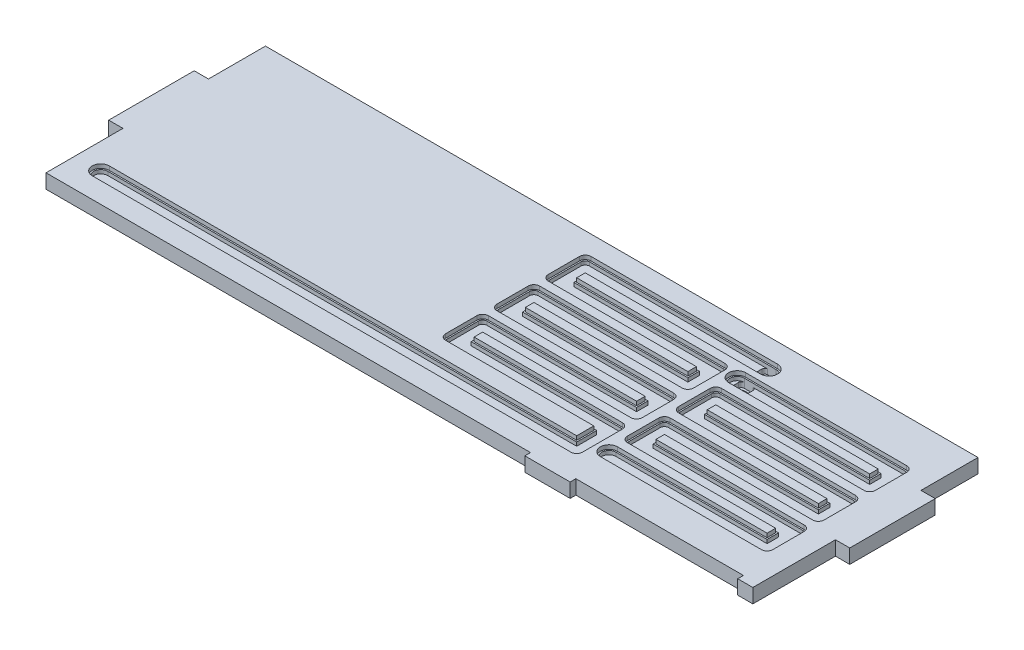
SolidWorks part; units mm, degrees
ref_plane "前视基准面" through (0, 0, 0) normal (0, 0, 1) x (1, 0, 0)
ref_plane "上视基准面" through (0, 0, 0) normal (0, 1, 0) x (1, 0, 0)
ref_plane "右视基准面" through (0, 0, 0) normal (1, 0, 0) x (0, 0, -1)
sketch "草图1" plane through (0, 0, 0) normal (0, 1, 0) x (1, 0, 0)
  line L0 (0, 0) -> (0, -200)
  line L1 (0, -200) -> (-50, -200)
  line L2 (-50, -200) -> (-50, -500)
  line L3 (-50, -500) -> (0, -500)
  line L4 (0, -500) -> (0, -770)
  line L5 (0, -770) -> (1700, -770)
  line L6 (1700, -770) -> (1700, -790)
  line L7 (1700, -790) -> (1859, -790)
  line L8 (1859, -790) -> (1859, -770)
  line L9 (1859, -770) -> (2447, -770)
  line L10 (2447, -770) -> (2447, -790)
  line L11 (2447, -790) -> (2500, -790)
  line L12 (2500, -790) -> (2500, -500)
  line L13 (2500, -500) -> (2550, -500)
  line L14 (2550, -500) -> (2550, -200)
  line L15 (2550, -200) -> (2500, -200)
  line L16 (2500, -200) -> (2500, 0)
  line L17 (2500, 0) -> (0, 0)
  line L18 (90, -668) -> (1760, -668)
  line L19 (1760, -668) -> (1760, -548)
  line L20 (1760, -548) -> (1220, -548)
  line L21 (1220, -548) -> (1220, -458)
  line L22 (1220, -458) -> (1760, -458)
  line L23 (1760, -458) -> (1760, -368)
  line L24 (1760, -368) -> (1220, -368)
  line L25 (1220, -368) -> (1220, -278)
  line L26 (1220, -278) -> (1760, -278)
  line L27 (1760, -278) -> (1760, -188)
  line L28 (1760, -188) -> (1220, -188)
  line L29 (1220, -188) -> (1220, -98)
  line L30 (1220, -98) -> (1865, -98)
  line L31 (1835, -180) -> (2390, -180)
  line L32 (2390, -180) -> (2390, -270)
  line L33 (2390, -270) -> (1850, -270)
  line L34 (1850, -270) -> (1850, -360)
  line L35 (1850, -360) -> (2390, -360)
  line L36 (2390, -360) -> (2390, -450)
  line L37 (2390, -450) -> (1850, -450)
  line L38 (1850, -450) -> (1850, -540)
  line L39 (1850, -540) -> (2390, -540)
  line L40 (2390, -540) -> (2390, -630)
  line L41 (2390, -630) -> (1835, -630)
  line L42 (90, -698) -> (1770, -698)
  line L43 (1790, -678) -> (1790, -538)
  line L44 (1770, -518) -> (1250, -518)
  line L45 (1250, -518) -> (1250, -488)
  line L46 (1250, -488) -> (1770, -488)
  line L47 (1790, -468) -> (1790, -358)
  line L48 (1770, -338) -> (1250, -338)
  line L49 (1250, -338) -> (1250, -308)
  line L50 (1250, -308) -> (1770, -308)
  line L51 (1790, -288) -> (1790, -178)
  line L52 (1770, -158) -> (1250, -158)
  line L53 (1250, -158) -> (1250, -128)
  line L54 (1250, -128) -> (1865, -128)
  line L55 (90, -638) -> (1730, -638)
  line L56 (1730, -638) -> (1730, -578)
  line L57 (1730, -578) -> (1210, -578)
  line L58 (1190, -558) -> (1190, -448)
  line L59 (1210, -428) -> (1730, -428)
  line L60 (1730, -428) -> (1730, -398)
  line L61 (1730, -398) -> (1210, -398)
  line L62 (1190, -378) -> (1190, -268)
  line L63 (1210, -248) -> (1730, -248)
  line L64 (1730, -248) -> (1730, -218)
  line L65 (1730, -218) -> (1210, -218)
  line L66 (1190, -198) -> (1190, -88)
  line L67 (1210, -68) -> (1865, -68)
  line L68 (1790, -308) -> (1790, -158) construction
  line L69 (1790, -158) -> (1250, -158) construction
  line L70 (1250, -308) -> (1790, -308) construction
  line L71 (1790, -488) -> (1790, -338) construction
  line L72 (1790, -338) -> (1250, -338) construction
  line L73 (1250, -488) -> (1790, -488) construction
  line L74 (1790, -698) -> (1790, -518) construction
  line L75 (1790, -518) -> (1250, -518) construction
  line L76 (90, -698) -> (1790, -698) construction
  line L77 (1730, -578) -> (1190, -578) construction
  line L78 (1190, -578) -> (1190, -428) construction
  line L79 (1190, -428) -> (1730, -428) construction
  line L80 (1730, -398) -> (1190, -398) construction
  line L81 (1190, -398) -> (1190, -248) construction
  line L82 (1190, -248) -> (1730, -248) construction
  line L83 (1730, -218) -> (1190, -218) construction
  line L84 (1190, -218) -> (1190, -68) construction
  line L85 (1190, -68) -> (1865, -68) construction
  line L86 (90, -693) -> (1770, -693)
  line L87 (1785, -678) -> (1785, -538)
  line L88 (1770, -523) -> (1245, -523)
  line L89 (1245, -523) -> (1245, -483)
  line L90 (1245, -483) -> (1770, -483)
  line L91 (1785, -468) -> (1785, -358)
  line L92 (1770, -343) -> (1245, -343)
  line L93 (1245, -343) -> (1245, -303)
  line L94 (1245, -303) -> (1770, -303)
  line L95 (1785, -288) -> (1785, -178)
  line L96 (1770, -163) -> (1245, -163)
  line L97 (1245, -163) -> (1245, -123)
  line L98 (1245, -123) -> (1865, -123)
  line L99 (1210, -73) -> (1865, -73)
  line L100 (1195, -198) -> (1195, -88)
  line L101 (1735, -213) -> (1210, -213)
  line L102 (1735, -253) -> (1735, -213)
  line L103 (1210, -253) -> (1735, -253)
  line L104 (1195, -378) -> (1195, -268)
  line L105 (1735, -393) -> (1210, -393)
  line L106 (1735, -433) -> (1735, -393)
  line L107 (1210, -433) -> (1735, -433)
  line L108 (1195, -558) -> (1195, -448)
  line L109 (1735, -573) -> (1210, -573)
  line L110 (1735, -643) -> (1735, -573)
  line L111 (90, -643) -> (1735, -643)
  line L112 (1835, -210) -> (2360, -210)
  line L113 (2360, -210) -> (2360, -240)
  line L114 (2360, -240) -> (1840, -240)
  line L115 (1820, -260) -> (1820, -370)
  line L116 (1840, -390) -> (2360, -390)
  line L117 (2360, -390) -> (2360, -420)
  line L118 (2360, -420) -> (1840, -420)
  line L119 (1820, -440) -> (1820, -550)
  line L120 (1840, -570) -> (2360, -570)
  line L121 (2360, -570) -> (2360, -600)
  line L122 (2360, -600) -> (1835, -600)
  line L123 (1835, -150) -> (2400, -150)
  line L124 (2420, -170) -> (2420, -280)
  line L125 (2400, -300) -> (1880, -300)
  line L126 (1880, -300) -> (1880, -330)
  line L127 (1880, -330) -> (2400, -330)
  line L128 (2420, -350) -> (2420, -460)
  line L129 (2400, -480) -> (1880, -480)
  line L130 (1880, -480) -> (1880, -510)
  line L131 (1880, -510) -> (2400, -510)
  line L132 (2420, -530) -> (2420, -640)
  line L133 (2400, -660) -> (1835, -660)
  line L134 (2360, -240) -> (1820, -240) construction
  line L135 (1820, -240) -> (1820, -390) construction
  line L136 (1820, -390) -> (2360, -390) construction
  line L137 (2360, -420) -> (1820, -420) construction
  line L138 (1820, -420) -> (1820, -570) construction
  line L139 (1820, -570) -> (2360, -570) construction
  line L140 (2420, -510) -> (2420, -660) construction
  line L141 (2420, -660) -> (1835, -660) construction
  line L142 (1880, -510) -> (2420, -510) construction
  line L143 (2420, -330) -> (2420, -480) construction
  line L144 (2420, -480) -> (1880, -480) construction
  line L145 (1880, -330) -> (2420, -330) construction
  line L146 (2420, -300) -> (1880, -300) construction
  line L147 (2420, -150) -> (2420, -300) construction
  line L148 (1835, -150) -> (2420, -150) construction
  line L149 (1835, -155) -> (2400, -155)
  line L150 (2415, -170) -> (2415, -280)
  line L151 (2400, -295) -> (1875, -295)
  line L152 (1875, -295) -> (1875, -335)
  line L153 (1875, -335) -> (2400, -335)
  line L154 (2415, -350) -> (2415, -460)
  line L155 (2400, -475) -> (1875, -475)
  line L156 (1875, -475) -> (1875, -515)
  line L157 (1875, -515) -> (2400, -515)
  line L158 (2415, -530) -> (2415, -640)
  line L159 (2400, -655) -> (1835, -655)
  line L160 (2365, -605) -> (1835, -605)
  line L161 (2365, -565) -> (2365, -605)
  line L162 (1840, -565) -> (2365, -565)
  line L163 (1825, -440) -> (1825, -550)
  line L164 (2365, -425) -> (1840, -425)
  line L165 (2365, -385) -> (2365, -425)
  line L166 (1840, -385) -> (2365, -385)
  line L167 (1825, -260) -> (1825, -370)
  line L168 (2365, -245) -> (1840, -245)
  line L169 (2365, -205) -> (2365, -245)
  line L170 (1835, -205) -> (2365, -205)
  arc A0 (90, -698) -> (90, -638) centre (90, -668) cw
  arc A1 (1865, -128) -> (1865, -68) centre (1865, -98) ccw
  arc A2 (1790, -178) -> (1770, -158) centre (1770, -178) ccw
  arc A3 (1770, -308) -> (1790, -288) centre (1770, -288) ccw
  arc A4 (1790, -358) -> (1770, -338) centre (1770, -358) ccw
  arc A5 (1770, -488) -> (1790, -468) centre (1770, -468) ccw
  arc A6 (1790, -538) -> (1770, -518) centre (1770, -538) ccw
  arc A7 (1770, -698) -> (1790, -678) centre (1770, -678) ccw
  arc A8 (1210, -578) -> (1190, -558) centre (1210, -558) cw
  arc A9 (1190, -448) -> (1210, -428) centre (1210, -448) cw
  arc A10 (1210, -398) -> (1190, -378) centre (1210, -378) cw
  arc A11 (1190, -268) -> (1210, -248) centre (1210, -268) cw
  arc A12 (1210, -218) -> (1190, -198) centre (1210, -198) cw
  arc A13 (1190, -88) -> (1210, -68) centre (1210, -88) cw
  arc A14 (1770, -693) -> (1785, -678) centre (1770, -678) ccw
  arc A15 (1785, -538) -> (1770, -523) centre (1770, -538) ccw
  arc A16 (1770, -483) -> (1785, -468) centre (1770, -468) ccw
  arc A17 (1785, -358) -> (1770, -343) centre (1770, -358) ccw
  arc A18 (1770, -303) -> (1785, -288) centre (1770, -288) ccw
  arc A19 (1785, -178) -> (1770, -163) centre (1770, -178) ccw
  arc A20 (1865, -123) -> (1865, -73) centre (1865, -98) ccw
  arc A21 (1195, -88) -> (1210, -73) centre (1210, -88) cw
  arc A22 (1210, -213) -> (1195, -198) centre (1210, -198) cw
  arc A23 (1195, -268) -> (1210, -253) centre (1210, -268) cw
  arc A24 (1210, -393) -> (1195, -378) centre (1210, -378) cw
  arc A25 (1195, -448) -> (1210, -433) centre (1210, -448) cw
  arc A26 (1210, -573) -> (1195, -558) centre (1210, -558) cw
  arc A27 (90, -693) -> (90, -643) centre (90, -668) cw
  arc A28 (1835, -210) -> (1835, -150) centre (1835, -180) cw
  arc A29 (1835, -600) -> (1835, -660) centre (1835, -630) ccw
  arc A30 (1840, -240) -> (1820, -260) centre (1840, -260) ccw
  arc A31 (1820, -370) -> (1840, -390) centre (1840, -370) ccw
  arc A32 (1840, -420) -> (1820, -440) centre (1840, -440) ccw
  arc A33 (1820, -550) -> (1840, -570) centre (1840, -550) ccw
  arc A34 (2420, -640) -> (2400, -660) centre (2400, -640) cw
  arc A35 (2400, -510) -> (2420, -530) centre (2400, -530) cw
  arc A36 (2420, -460) -> (2400, -480) centre (2400, -460) cw
  arc A37 (2400, -330) -> (2420, -350) centre (2400, -350) cw
  arc A38 (2400, -300) -> (2420, -280) centre (2400, -280) ccw
  arc A39 (2400, -150) -> (2420, -170) centre (2400, -170) cw
  arc A40 (2400, -155) -> (2415, -170) centre (2400, -170) cw
  arc A41 (2400, -295) -> (2415, -280) centre (2400, -280) ccw
  arc A42 (2400, -335) -> (2415, -350) centre (2400, -350) cw
  arc A43 (2415, -460) -> (2400, -475) centre (2400, -460) cw
  arc A44 (2400, -515) -> (2415, -530) centre (2400, -530) cw
  arc A45 (2415, -640) -> (2400, -655) centre (2400, -640) cw
  arc A46 (1835, -605) -> (1835, -655) centre (1835, -630) ccw
  arc A47 (1825, -550) -> (1840, -565) centre (1840, -550) ccw
  arc A48 (1840, -425) -> (1825, -440) centre (1840, -440) ccw
  arc A49 (1825, -370) -> (1840, -385) centre (1840, -370) ccw
  arc A50 (1840, -245) -> (1825, -260) centre (1840, -260) ccw
  arc A51 (1835, -205) -> (1835, -155) centre (1835, -180) cw
  point P45 (0, 0)
  point P46 (0, 0)
  point P47 (1858.5859, -180)
  point P48 (0, 0)
  point P267 (0, 0)
  point P268 (0, 0)
  point P269 (0, 0)
  point P270 (0, 0)
  point P271 (1840.0691, -180)
  point P272 (1895, -98)
  point P273 (1805, -180)
  point P274 (0, 0)
  dimension "D35" = 20
  dimension "D39" = 20
  dimension "D1" = 2600
  dimension "D2" = 790
  dimension "D3" = 20
  dimension "D4" = 50
  dimension "D5" = 2500
  dimension "D6" = 770
  dimension "D7" = 800
  dimension "D8" = 53
  dimension "D9" = 588
  dimension "D10" = 200
  dimension "D11" = 300
  dimension "D12" = 200
  dimension "D13" = 300
  dimension "D14" = 140
  dimension "D15" = 102
  dimension "D16" = 120
  dimension "D17" = 90
  dimension "D18" = 90
  dimension "D19" = 90
  dimension "D20" = 90
  dimension "D21" = 90
  dimension "D22" = 180
  dimension "D23" = 90
  dimension "D24" = 90
  dimension "D25" = 90
  dimension "D26" = 90
  dimension "D27" = 90
  dimension "D28" = 110
  dimension "D29" = 635
  dimension "D30" = 540
  dimension "D31" = 90
  dimension "D32" = 540
  dimension "D41" = 90
  dimension "D33" = 30
  dimension "D34" = 30
  dimension "D36" = 5
  dimension "D37" = 30
  dimension "D38" = 30
  dimension "D40" = 5
extrude "凸台-拉伸1" add sketch "草图1" against normal blind 50 contours L17 L0 L1 L2 L3 L4 L5 L6 L7 L8 L9 L10 L11 L12 L13 L14 L15 L16
extrude "切除-拉伸1" cut sketch "草图1<3>" against normal blind 14 contours L42 A7 L43 A6 L44 L45 L46 A5 L47 A4 L48 L49 L50 A3 L51 A2 L52 L53 L54 A1 L67 A13 L66 A12 L65 L64 L63 A11 L62 A10 L61 L60 L59 A9 L58 A8 L57 L56 L55 A0 | L133 A29 L122 L121 L120 A33 L119 A32 L118 L117 L116 A31 L115 A30 L114 L113 L112 A28 L123 A39 L124 A38 L125 L126 L127 A37 L128 A36 L129 L130 L131 A35 L132 A34
sketch "草图1<3>" plane through (0, 0, 0) normal (0, 1, 0) x (1, 0, 0) same geometry as "草图1"
extrude "切除-拉伸3" cut sketch "草图1<5>" against normal blind 27 contours L86 A14 L87 A15 L88 L89 L90 A16 L91 A17 L92 L93 L94 A18 L95 A19 L96 L97 L98 A20 L99 A21 L100 A22 L101 L102 L103 A23 L104 A24 L105 L106 L107 A25 L108 A26 L109 L110 L111 A27 | L159 A46 L160 L161 L162 A47 L163 A48 L164 L165 L166 A49 L167 A50 L168 L169 L170 A51 L149 A40 L150 A41 L151 L152 L153 A42 L154 A43 L155 L156 L157 A44 L158 A45
sketch "草图1<5>" plane through (0, 0, 0) normal (0, 1, 0) x (1, 0, 0) same geometry as "草图1"
sketch "草图2" plane through (0, 0, 0) normal (0, 1, 0) x (1, 0, 0)
  line L0 (1220, -98) -> (1865, -98) construction
  line L1 (1865, -123) -> (1835, -123)
  line L2 (1875, -113) -> (1875, -83)
  line L3 (1865, -73) -> (1835, -73)
  line L4 (1825, -113) -> (1825, -83)
  line L5 (1875, -123) -> (1825, -73) construction
  line L6 (1875, -73) -> (1825, -123) construction
  line L7 (2500, -200) -> (2500, 0) construction
  line L8 (1835, -180) -> (2390, -180) construction
  line L9 (1865, -205) -> (1835, -205)
  line L10 (1875, -195) -> (1875, -165)
  line L11 (1865, -155) -> (1835, -155)
  line L12 (1825, -195) -> (1825, -165)
  line L13 (1875, -205) -> (1825, -155) construction
  line L14 (1875, -155) -> (1825, -205) construction
  line L16 (1857.5, -115.5) -> (1842.5, -115.5)
  line L17 (1867.5, -105.5) -> (1867.5, -90.5)
  line L18 (1857.5, -80.5) -> (1842.5, -80.5)
  line L19 (1832.5, -105.5) -> (1832.5, -90.5)
  line L20 (1867.5, -115.5) -> (1832.5, -80.5) construction
  line L21 (1867.5, -80.5) -> (1832.5, -115.5) construction
  line L22 (1857.5, -197.5) -> (1842.5, -197.5)
  line L23 (1867.5, -187.5) -> (1867.5, -172.5)
  line L24 (1857.5, -162.5) -> (1842.5, -162.5)
  line L25 (1832.5, -187.5) -> (1832.5, -172.5)
  line L26 (1867.5, -197.5) -> (1832.5, -162.5) construction
  line L27 (1867.5, -162.5) -> (1832.5, -197.5) construction
  arc A0 (1865, -128) -> (1865, -68) centre (1865, -98) ccw construction
  arc A1 (1865, -128) -> (1865, -68) centre (1865, -98) ccw
  arc A2 (1835, -150) -> (1835, -210) centre (1835, -180) ccw construction
  arc A3 (1835, -150) -> (1835, -210) centre (1835, -180) ccw
  arc A4 (1865, -205) -> (1875, -195) centre (1865, -195) ccw
  arc A5 (1857.5, -197.5) -> (1867.5, -187.5) centre (1857.5, -187.5) ccw
  arc A6 (1842.5, -197.5) -> (1832.5, -187.5) centre (1842.5, -187.5) cw
  arc A7 (1835, -205) -> (1825, -195) centre (1835, -195) cw
  arc A8 (1842.5, -162.5) -> (1832.5, -172.5) centre (1842.5, -172.5) ccw
  arc A9 (1835, -155) -> (1825, -165) centre (1835, -165) ccw
  arc A10 (1867.5, -172.5) -> (1857.5, -162.5) centre (1857.5, -172.5) ccw
  arc A11 (1875, -165) -> (1865, -155) centre (1865, -165) ccw
  arc A12 (1865, -123) -> (1875, -113) centre (1865, -113) ccw
  arc A13 (1857.5, -115.5) -> (1867.5, -105.5) centre (1857.5, -105.5) ccw
  arc A14 (1835, -123) -> (1825, -113) centre (1835, -113) cw
  arc A15 (1842.5, -115.5) -> (1832.5, -105.5) centre (1842.5, -105.5) cw
  arc A16 (1842.5, -80.5) -> (1832.5, -90.5) centre (1842.5, -90.5) ccw
  arc A17 (1867.5, -90.5) -> (1857.5, -80.5) centre (1857.5, -90.5) ccw
  arc A18 (1875, -83) -> (1865, -73) centre (1865, -83) ccw
  arc A19 (1835, -73) -> (1825, -83) centre (1835, -83) ccw
  point P0 (1850, -98)
  point P9 (1850, -180)
  point P16 (1850, -180)
  point P21 (1850, -98)
  dimension "D6" = 35
  dimension "D10" = 10
  dimension "D1" = 50
  dimension "D2" = 50
  dimension "D3" = 650
  dimension "D4" = 50
  dimension "D5" = 50
  dimension "D7" = 35
  dimension "D8" = 35
  dimension "D9" = 35
extrude "切除-拉伸4" cut sketch "草图2" against normal blind 45 contours L4 A19 L3 A18 L2 A12 L1 A14 | L12 A9 L11 A11 L10 A4 L9 A7
extrude "切除-拉伸6" cut sketch "草图2<4>" against normal blind 50 contours L23 A10 L24 A8 L25 A6 L22 A5 | L18 A16 L19 A15 L16 A13 L17 A17 region at (1850, 0, 180)
sketch "草图2<4>" plane through (0, 0, 0) normal (0, 1, 0) x (1, 0, 0) same geometry as "草图2"
sketch "草图3" plane through (0, -50, 0) normal (0, -1, 0) x (1, 0, 0)
  line L0 (2500, 0) -> (0, 0) construction
  line L1 (370, 110) -> (120, 110) construction
  line L2 (370, 110) -> (370, 420) construction
  line L3 (370, 420) -> (120, 420) construction
  line L4 (120, 110) -> (120, 420) construction
  line L5 (370, 110) -> (120, 420) construction
  line L6 (370, 420) -> (120, 110) construction
  line L7 (772, 20) -> (432, 20) construction
  line L8 (772, 20) -> (772, 260) construction
  line L9 (772, 260) -> (432, 260) construction
  line L10 (432, 20) -> (432, 260) construction
  line L11 (772, 20) -> (432, 260) construction
  line L12 (772, 260) -> (432, 20) construction
  line L17 (864, 85) -> (1109, 85) construction
  line L18 (864, 220) -> (1109, 220) construction
  line L23 (864, 340) -> (1109, 340) construction
  line L24 (889, 460) -> (1084, 460) construction
  line L29 (622, 525) -> (1062, 525) construction
  line L30 (480, 475) -> (810, 475) construction
  line L31 (0, 0) -> (0, 200) construction
  line L32 (480, 475) -> (480, 310) construction
  line L33 (480, 310) -> (810, 310) construction
  line L34 (810, 475) -> (810, 310) construction
  line L35 (622, 625) -> (1062, 625) construction
  line L36 (622, 715) -> (1062, 715) construction
  line L37 (0, 770) -> (1700, 770) construction
  line L38 (772, 715) -> (772, 525) construction
  line L39 (1062, 715) -> (1062, 525) construction
  line L40 (912, 715) -> (912, 525) construction
  line L41 (622, 605) -> (1062, 605) construction
  line L42 (842, 596.5572) -> (842, 560.0537) construction
  line L43 (622, 585) -> (1062, 585) construction
  line L44 (987, 615.5371) -> (987, 560.0537) construction
  line L45 (697, 615.5371) -> (697, 560.0537) construction
  line L46 (697, 596.5572) -> (697, 560.0537) construction
  line L47 (987, 596.5572) -> (987, 560.0537) construction
  line L48 (622, 525) -> (542, 525) construction
  line L49 (1277, 58) -> (1464, 58) construction
  line L50 (1242, 651) -> (1542, 651)
  line L51 (1602, 704.5) -> (1857, 704.5) construction
  line L52 (1532, 20) -> (1777, 20) construction
  line L53 (2500, 200) -> (2500, 0) construction
  line L54 (1967, 678) -> (2357, 678) construction
  line L55 (1967, 678) -> (1967, 48) construction
  line L56 (1967, 48) -> (2357, 48) construction
  line L57 (2357, 678) -> (2357, 48) construction
  circle A0 centre (120, 420) radius 3.35
  circle A1 centre (370, 420) radius 3.35
  circle A2 centre (370, 110) radius 3.35
  circle A3 centre (120, 110) radius 3.35
  circle A4 centre (120, 265) radius 3.35
  circle A5 centre (370, 265) radius 3.35
  circle A6 centre (245, 265) radius 4.25
  circle A7 centre (432, 260) radius 3.35
  circle A8 centre (602, 260) radius 3.35
  circle A9 centre (772, 260) radius 3.35
  circle A10 centre (772, 140) radius 3.35
  circle A11 centre (772, 20) radius 3.35
  circle A12 centre (602, 20) radius 3.35
  circle A13 centre (432, 20) radius 3.35
  circle A14 centre (602, 140) radius 4.25
  circle A15 centre (432, 140) radius 3.35
  circle A16 centre (864, 340) radius 3.35
  circle A17 centre (1109, 340) radius 3.35
  circle A18 centre (1109, 220) radius 3.35
  circle A19 centre (864, 220) radius 3.35
  circle A20 centre (864, 85) radius 3.35
  circle A21 centre (1109, 85) radius 3.35
  circle A22 centre (986.5, 220) radius 4.25
  circle A23 centre (1084, 460) radius 3.35
  circle A24 centre (889, 460) radius 3.35
  circle A25 centre (480, 475) radius 5.25
  circle A26 centre (480, 310) radius 5.25
  circle A27 centre (810, 475) radius 5.25
  circle A28 centre (810, 310) radius 5.25
  circle A29 centre (622, 715) radius 3.35
  circle A30 centre (622, 625) radius 3.35
  circle A31 centre (622, 525) radius 3.35
  circle A32 centre (772, 525) radius 3.35
  circle A33 centre (912, 525) radius 3.35
  circle A34 centre (1062, 525) radius 3.35
  circle A35 centre (1062, 625) radius 3.35
  circle A36 centre (1062, 715) radius 3.35
  circle A37 centre (912, 715) radius 3.35
  circle A38 centre (772, 715) radius 3.35
  circle A39 centre (912, 625) radius 3.35
  circle A40 centre (772, 625) radius 3.35
  circle A41 centre (697, 605) radius 4.25
  circle A43 centre (987, 605) radius 4.25
  circle A44 centre (842, 585) radius 4.25
  circle A45 centre (542, 525) radius 2.5
  circle A46 centre (1277, 58) radius 4.25
  circle A47 centre (1297, 58) radius 4.25
  circle A48 centre (1432, 58) radius 4.25
  circle A49 centre (1464, 58) radius 4.25
  circle A51 centre (1242, 651) radius 3.35
  circle A52 centre (1317, 651) radius 3.35
  circle A53 centre (1467, 651) radius 3.35
  circle A54 centre (1392, 651) radius 3.35
  circle A55 centre (1542, 651) radius 3.35
  circle A56 centre (1777, 20) radius 4.25
  circle A57 centre (1747, 20) radius 4.25
  circle A58 centre (1562, 20) radius 4.25
  circle A59 centre (1532, 20) radius 4.25
  circle A60 centre (1857, 704.5) radius 3.35
  circle A61 centre (1602, 704.5) radius 3.35
  circle A62 centre (1644.5, 704.5) radius 3.35
  circle A63 centre (1814.5, 704.5) radius 3.35
  circle A64 centre (1687, 704.5) radius 3.35
  circle A65 centre (1772, 704.5) radius 3.35
  circle A66 centre (1729.5, 704.5) radius 3.35
  circle A67 centre (1967, 678) radius 7
  circle A68 centre (2357, 678) radius 7
  circle A69 centre (2357, 48) radius 7
  circle A70 centre (1967, 48) radius 7
  circle A71 centre (245, 265) radius 35
  circle A72 centre (120, 420) radius 20
  circle A73 centre (120, 265) radius 20
  circle A74 centre (120, 110) radius 20
  circle A75 centre (370, 110) radius 20
  circle A76 centre (432, 140) radius 20
  circle A77 centre (370, 265) radius 20
  circle A78 centre (432, 260) radius 20
  circle A79 centre (602, 260) radius 20
  circle A80 centre (602, 140) radius 35
  circle A82 centre (432, 20) radius 20
  circle A83 centre (602, 20) radius 20
  circle A84 centre (772, 140) radius 20
  circle A85 centre (772, 20) radius 20
  circle A86 centre (772, 260) radius 20
  circle A88 centre (370, 420) radius 20
  circle A91 centre (622, 525) radius 20
  circle A92 centre (772, 525) radius 20
  circle A93 centre (842, 585) radius 35
  circle A94 centre (697, 605) radius 35
  circle A95 centre (622, 625) radius 20
  circle A96 centre (912, 525) radius 20
  circle A97 centre (622, 715) radius 20
  circle A98 centre (772, 715) radius 20
  circle A99 centre (912, 715) radius 20
  circle A100 centre (1062, 715) radius 20
  circle A101 centre (1062, 625) radius 20
  circle A102 centre (912, 625) radius 20
  circle A103 centre (772, 625) radius 20
  circle A104 centre (987, 605) radius 35
  circle A105 centre (1062, 525) radius 20
  circle A106 centre (1084, 460) radius 20
  circle A107 centre (889, 460) radius 20
  circle A108 centre (1109, 340) radius 20
  circle A109 centre (864, 340) radius 20
  circle A110 centre (864, 220) radius 20
  circle A111 centre (986.5, 220) radius 35
  circle A112 centre (1109, 220) radius 20
  circle A113 centre (1109, 85) radius 20
  circle A114 centre (864, 85) radius 20
  point P0 (245, 265)
  point P5 (602, 140)
  dimension "D6" = 6.7
  dimension "D7" = 8.5
  dimension "D13" = 6.7
  dimension "D14" = 8.5
  dimension "D19" = 6.7
  dimension "D20" = 8.5
  dimension "D25" = 6.7
  dimension "D29" = 10.5
  dimension "D38" = 6.7
  dimension "D44" = 8.5
  dimension "D46" = 5
  dimension "D49" = 8.5
  dimension "D55" = 6.7
  dimension "D64" = 8.5
  dimension "D77" = 14
  dimension "D78" = 40
  dimension "D79" = 70
  dimension "D1" = 110
  dimension "D2" = 155
  dimension "D3" = 155
  dimension "D4" = 120
  dimension "D5" = 250
  dimension "D8" = 62
  dimension "D9" = 170
  dimension "D10" = 170
  dimension "D11" = 20
  dimension "D12" = 120
  dimension "D15" = 92
  dimension "D16" = 65
  dimension "D17" = 135
  dimension "D18" = 120
  dimension "D21" = 120
  dimension "D22" = 25
  dimension "D23" = 195
  dimension "D24" = 245
  dimension "D26" = 48
  dimension "D27" = 330
  dimension "D28" = 165
  dimension "D30" = 50
  dimension "D31" = 142
  dimension "D32" = 100
  dimension "D33" = 145
  dimension "D34" = 90
  dimension "D35" = 150
  dimension "D36" = 140
  dimension "D37" = 150
  dimension "D40" = 70
  dimension "D45" = 80
  dimension "D47" = 58
  dimension "D48" = 168
  dimension "D50" = 20
  dimension "D51" = 135
  dimension "D52" = 32
  dimension "D54" = 133
  dimension "D53" = 593
  dimension "D56" = 75
  dimension "D57" = 75
  dimension "D58" = 75
  dimension "D59" = 75
  dimension "D60" = 60
  dimension "D61" = 143
  dimension "D62" = 390
  dimension "D63" = 190
  dimension "D65" = 30
  dimension "D66" = 245
  dimension "D67" = 30
  dimension "D68" = 684.5
  dimension "D69" = 42.5
  dimension "D70" = 85
  dimension "D71" = 85
  dimension "D72" = 85
  dimension "D73" = 42.5
  dimension "D74" = 42.5
  dimension "D75" = 48
  dimension "D76" = 630
  dimension "D39" = 20
  dimension "D41" = 40
  dimension "D42" = 145
  dimension "D43" = 145
